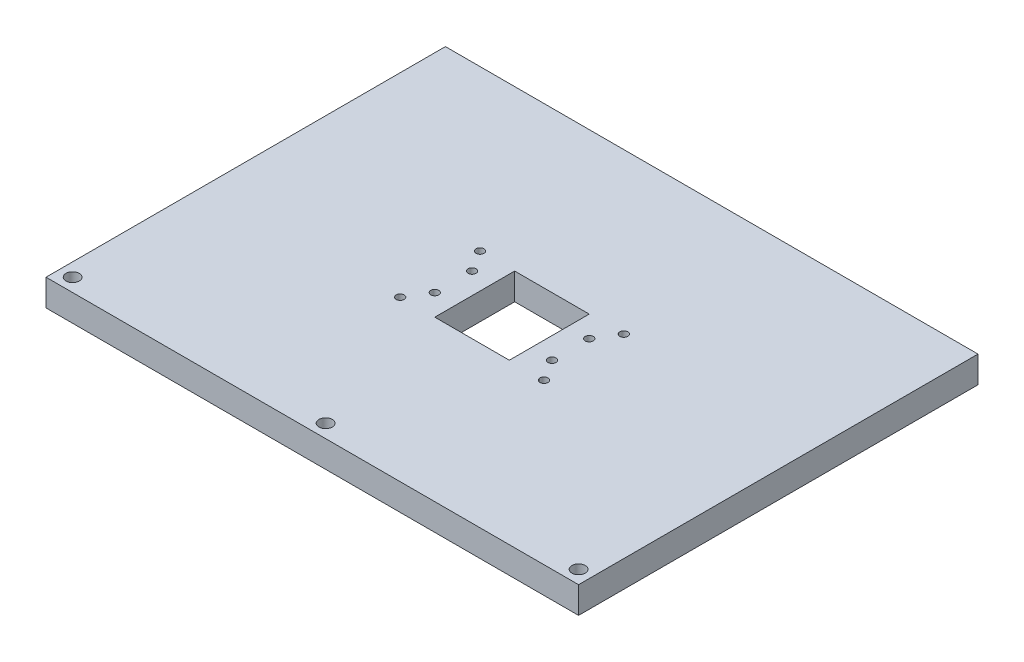
SolidWorks part; units mm, degrees
material "Perspex (TM) GS Acrylic Cast Sheet"
ref_plane "Front Plane" through (0, 0, 0) normal (0, 0, 1) x (1, 0, 0)
ref_plane "Top Plane" through (0, 0, 0) normal (0, 1, 0) x (1, 0, 0)
ref_plane "Right Plane" through (0, 0, 0) normal (1, 0, 0) x (0, 0, -1)
sketch "Sketch1" plane through (0, 0, 0) normal (0, 0, 1) x (1, 0, 0)
  line L1 (-100, 30) -> (100, 30)
  line L2 (-100, 30) -> (-100, -30)
  line L3 (-100, -30) -> (100, -30)
  line L4 (100, 30) -> (100, -30)
  line L5 (-100, 30) -> (100, -30) construction
  line L6 (-100, -30) -> (100, 30) construction
  point P0 (0, 0)
  dimension "D1" = 200
  dimension "D2" = 60
extrude "Boss-Extrude1" add sketch "Sketch1" along normal blind 10
sketch "Sketch2" plane through (0, 0, 0) normal (0, 0, -1) x (-1, 0, 0)
  line L0 (-100, -30) -> (-100, -20)
  line L1 (-100, -30) -> (-100, 30) construction
  line L2 (-100, -20) -> (100, -20)
  line L3 (100, 30) -> (100, -30) construction
  line L4 (100, -20) -> (100, -30)
  line L5 (100, -30) -> (-100, -30)
  dimension "D1" = 10
extrude "Boss-Extrude2" add sketch "Sketch2" along normal blind 140
sketch "Sketch3" plane through (0, 0, 10) normal (0, 0, 1) x (1, 0, 0)
  line L1 (0, -5.5) -> (0, 5.5) construction
  line L2 (-100, -30) -> (100, -30) construction
  circle A0 centre (0, 5) radius 15.5
  circle A1 centre (60, 5) radius 15.5
  circle A2 centre (-60, 5) radius 15.5
  dimension "D1" = 31
  dimension "D2" = 35
  dimension "D3" = 60
  dimension "D4" = 60
extrude "Cut-Extrude1" cut sketch "Sketch3" against normal blind 60
sketch "Sketch7" plane through (0, -20, 0) normal (0, 1, 0) x (1, 0, 0)
  line L0 (0, -5.5) -> (0, 5.5) construction
  line L1 (4, 80) -> (14, 80)
  line L2 (4, 80) -> (4, 50)
  line L3 (4, 50) -> (14, 50)
  line L4 (14, 80) -> (14, 50)
  line L5 (4, 80) -> (14, 50) construction
  line L6 (4, 50) -> (14, 80) construction
  line L8 (0, 115.3101) -> (0, 11.0931) construction
  line L9 (-4, 50) -> (-14, 80) construction
  line L10 (-4, 80) -> (-14, 50) construction
  line L11 (-14, 80) -> (-14, 50)
  line L12 (-4, 50) -> (-14, 50)
  line L13 (-4, 80) -> (-4, 50)
  line L14 (-4, 80) -> (-14, 80)
  line L15 (-5.5, 0) -> (5.5, 0) construction
  point P0 (9, 65)
  point P16 (-9, 65)
  dimension "D1" = 10
  dimension "D2" = 30
  dimension "D3" = 4
  dimension "D4" = 65
extrude "Cut-Extrude4" cut sketch "Sketch7" against normal blind 30
sketch "Sketch9" plane through (0, -20, 0) normal (0, 1, 0) x (1, 0, 0)
  line L0 (0, -33) -> (0, 33) construction
  line L1 (-27, 80) -> (27, 80) construction
  line L2 (-27, 80) -> (-27, 50) construction
  line L3 (-27, 50) -> (27, 50) construction
  line L4 (27, 80) -> (27, 50) construction
  line L5 (-27, 80) -> (27, 50) construction
  line L6 (-27, 50) -> (27, 80) construction
  line L7 (-33, 0) -> (33, 0) construction
  line L8 (-4, 50) -> (-4, 80) construction
  line L9 (-14, 80) -> (-14, 50) construction
  line L10 (-4, 65) -> (-14, 65) construction
  line L11 (0, 98.8977) -> (0, 27.4847) construction
  line L12 (100, -10) -> (-100, -10) construction
  line L13 (-100, -10) -> (-100, 0) construction
  line L14 (100, -10) -> (100, 0) construction
  circle A0 centre (-27, 80) radius 1.5
  circle A1 centre (27, 80) radius 1.5
  circle A2 centre (27, 50) radius 1.5
  circle A3 centre (-27, 50) radius 1.5
  circle A6 centre (-22, 72) radius 1.5
  circle A7 centre (-22, 58) radius 1.5
  circle A8 centre (22, 72) radius 1.5
  circle A9 centre (22, 58) radius 1.5
  circle A12 centre (0, -5) radius 2.5
  circle A13 centre (95, -5) radius 2.5
  circle A14 centre (-95, -5) radius 2.5
  point P0 (0, 65)
  dimension "D1" = 3
  dimension "D7" = 8
  dimension "D8" = 14
  dimension "D10" = 7
  dimension "D11" = 5
  dimension "D12" = 5
  dimension "D13" = 5
  dimension "D14" = 5
  dimension "D2" = 30
  dimension "D3" = 54
  dimension "D4" = 65
extrude "Cut-Extrude6" cut sketch "Sketch9" against normal blind 20
sketch "Sketch10" plane through (0, 0, 0) normal (1, 0, 0) x (0, 0, -1)
  line L1 (0, -20) -> (-33.7656, -20)
  line L2 (0, -20) -> (0, 42.6278)
  line L3 (0, 42.6278) -> (-33.7656, 42.6278)
  line L4 (-33.7656, -20) -> (-33.7656, 42.6278)
extrude "Cut-Extrude7" cut sketch "Sketch10" against normal mid plane 260
sketch "Sketch11" plane through (0, -20, 0) normal (0, 1, 0) x (1, 0, 0)
  line L1 (-4, 80) -> (4, 80)
  line L2 (-4, 80) -> (-4, 50)
  line L3 (-4, 50) -> (4, 50)
  line L4 (4, 80) -> (4, 50)
extrude "Cut-Extrude8" cut sketch "Sketch11" against normal blind 30
